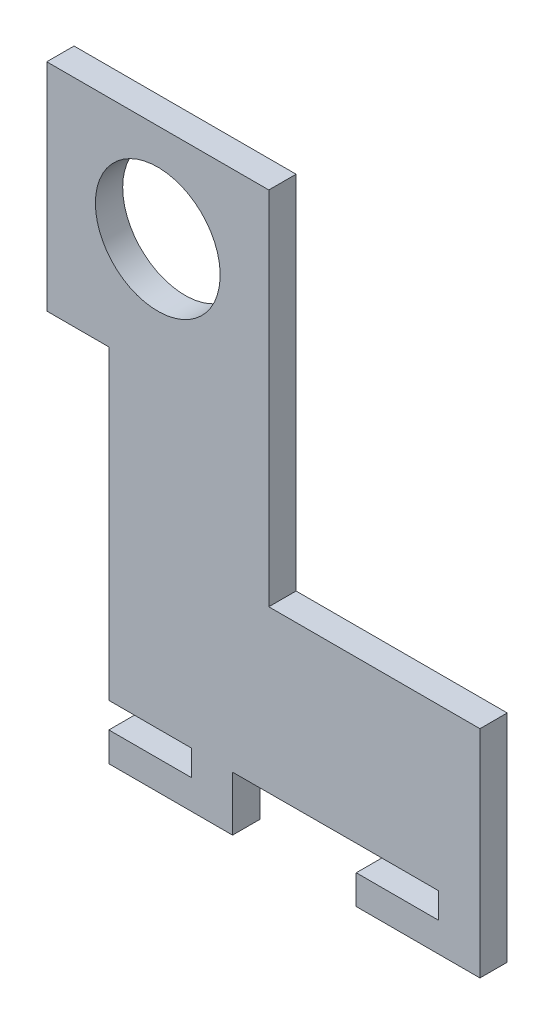
SolidWorks part; units mm, degrees
ref_plane "Front Plane" through (0, 0, 0) normal (0, 0, 1) x (1, 0, 0)
ref_plane "Top Plane" through (0, 0, 0) normal (0, 1, 0) x (1, 0, 0)
ref_plane "Right Plane" through (0, 0, 0) normal (1, 0, 0) x (0, 0, -1)
sketch "Sketch1" plane through (0, 0, 0) normal (0, 0, 1) x (1, 0, 0)
  line L1 (0, 0) -> (76.2, 0)
  line L2 (0, 0) -> (0, 96.6555)
  line L3 (0, 96.6555) -> (76.2, 96.6555)
  line L4 (76.2, 0) -> (76.2, 96.6555)
  line L5 (0, 0) -> (76.2, 96.6555) construction
  line L6 (0, 96.6555) -> (76.2, 0) construction
  point P4 (38.1, 48.3277)
  dimension "D1" = 96.6555
extrude "Boss-Extrude1" add sketch "Sketch1" along normal blind 4.8
sketch "Sketch2" plane through (0, 0, 0) normal (0, 0, -1) x (-1, 0, 0)
  circle A1 centre (-19.5293, 79.4008) radius 10.9746
  dimension "D1" = 21.9492
extrude "Cut-Extrude1" cut sketch "Sketch2" against normal through all
sketch "Sketch3" plane through (0, 0, 0) normal (0, -1, 0) x (1, 0, 0)
  line L1 (0, 0) -> (76.2, 0)
  line L2 (0, 0) -> (0, 4.8)
  line L3 (0, 4.8) -> (76.2, 4.8)
  line L4 (76.2, 0) -> (76.2, 4.8)
  line L5 (0, 0) -> (76.2, 4.8) construction
  line L6 (0, 4.8) -> (76.2, 0) construction
  point P4 (38.1, 2.4)
extrude "Boss-Extrude2" add sketch "Sketch3" along normal blind 4.826
sketch "Sketch5" plane through (0, 0, 0) normal (0, 0, -1) x (-1, 0, 0)
  line L1 (-76.2, 96.6555) -> (-39.0586, 96.6555)
  line L2 (-76.2, 96.6555) -> (-76.2, 33.1555)
  line L3 (-76.2, 33.1555) -> (-39.0586, 33.1555)
  line L4 (-39.0586, 96.6555) -> (-39.0586, 33.1555)
  line L5 (-76.2, 96.6555) -> (-39.0586, 33.1555) construction
  line L6 (-76.2, 33.1555) -> (-39.0586, 96.6555) construction
  point P4 (-57.6293, 64.9055)
  dimension "D1" = 37.1414
  dimension "D2" = 63.5
extrude "Cut-Extrude3" cut sketch "Sketch5" against normal through all
sketch "Sketch6" plane through (0, 0, 0) normal (0, 0, -1) x (-1, 0, 0)
  line L1 (0, -4.826) -> (-10.922, -4.826)
  line L2 (0, -4.826) -> (0, 58.674)
  line L3 (0, 58.674) -> (-10.922, 58.674)
  line L4 (-10.922, -4.826) -> (-10.922, 58.674)
  line L5 (0, -4.826) -> (-10.922, 58.674) construction
  line L6 (0, 58.674) -> (-10.922, -4.826) construction
  point P4 (-5.461, 26.924)
  dimension "D1" = 63.5
  dimension "D2" = 10.922
extrude "Cut-Extrude4" cut sketch "Sketch6" against normal blind 4.826
sketch "Sketch7" plane through (0, 0, 0) normal (0, 0, -1) x (-1, 0, 0)
  line L0 (-10.922, -4.826) -> (-76.2, -4.826) construction
  line L1 (-54.4407, -4.826) -> (-32.6813, -4.826)
  line L2 (-54.4407, -4.826) -> (-54.4407, 4.826)
  line L3 (-54.4407, 4.826) -> (-32.6813, 4.774)
  line L4 (-32.6813, -4.826) -> (-32.6813, 4.774)
  line L5 (-54.4407, -4.826) -> (-32.6813, 4.774) construction
  line L6 (-54.4407, 4.826) -> (-32.6813, -4.826) construction
  line L7 (-76.2, -4.826) -> (-54.4407, -4.826) construction
  line L8 (-10.922, -4.826) -> (-32.6813, -4.826) construction
  line L14 (-10.922, 58.674) -> (-10.922, -4.826) construction
  line L15 (-10.922, 4.826) -> (-25.4242, 4.826)
  line L21 (-10.922, 4.826) -> (-10.922, 0.326)
  line L22 (-10.922, 0.326) -> (-25.4242, 0.326)
  line L23 (-25.4242, 4.826) -> (-25.4242, 0.326)
  line L24 (-10.922, 4.826) -> (-25.4242, 0.326) construction
  line L25 (-10.922, 0.326) -> (-25.4242, 4.826) construction
  line L27 (-54.4407, 4.826) -> (-68.9429, 4.826)
  line L28 (-54.4407, 4.826) -> (-54.4407, 0.326)
  line L29 (-54.4407, 0.326) -> (-68.9429, 0.326)
  line L30 (-68.9429, 4.826) -> (-68.9429, 0.326)
  line L31 (-54.4407, 4.826) -> (-68.9429, 0.326) construction
  line L32 (-54.4407, 0.326) -> (-68.9429, 4.826) construction
  line L38 (-76.2, -4.826) -> (-76.2, 33.1555) construction
  point P4 (-43.5316, -0.013)
  point P15 (-18.1731, 2.576)
  point P21 (-61.6918, 2.576)
  line M13 (-10.922, -4.826) -> (-10.922, 58.674)
  line M20 (-76.2, -4.826) -> (-10.922, -4.826)
  dimension "D1" = 9.6
  dimension "D2" = 4.5
  dimension "D3" = 4.5
  dimension "D4" = 7.2571
  dimension "D5" = 7.2571
extrude "Cut-Extrude6" cut sketch "Sketch7" against normal through all contours L27 L30 L29 L2 | L4 L3 L2 M20 | L15 L23 L22 M13 region at (43.5708, -0.013, 0) region at (18.1731, 2.576, 0) region at (61.6918, 2.576, 0)
equation "\"MDF\"= 4.8mm"
equation "\"Foamcore\"= 4.6mm"
equation "\"PCB\" = 1.6mm"
equation "\"GMaterial\"= \"MDF\""
equation "\"BaseWidth\" = 10in"
equation "\"SkidLength\" = 1in"
equation "\"SkidClearance\" = 0.4in"
equation "\"MotorMountLength\" = 2in"
equation "\"MotorMountWidth\" = \"GMaterial\""
equation "\"MotorMountHeight\" = 2.25in"
equation "\"UnoStackWidth\" = 77.4mm"
equation "\"UnoStackLength\" = 79.8mm"
equation "\"UnoStackHeight\" = 34.2mm"
equation "\"TallHexRiserHeight\" = 22.2mm"
equation "\"PingPongBallSize\" = 40mm"
equation "\"BarrelLength\" = 9in"
equation "\"BarrelSize\" = \"PingPongBallSize\""
equation "\"PlatformLength\" = 4in"
equation "\"PlatformWidth\" = 6in"
equation "\"WheelDiameter\"=2.99213"
equation "\"ServoMountLength\"= 1.53774"
equation "\"ServoGearHeight\" = 0.95330261in"
equation "\"PlatformMountHeight\" = 3.19"
equation "\"PivotHoleRadius\"= 0.616358"
equation "\"D1@Sketch1\"=\"MDF\"+\"PivotHoleRadius\"+3"
equation "\"ServoMountReductionBackHeight\"=2.25"
equation "\"ServoMountHeight\"=2.49223"
equation "\"TensionOffSet\"= .3mm"
equation "\"MotorMountWedge\"=0.333333"
equation "\"LaserCutterOffset\"= .3mm"
equation "\"BumperWidth\"=11"
equation "\"PitcherWheelCompression\" = 2.5mm"
equation "\"PitchingWheelWidth\" = 26.2mm"
equation "\"PitchingWheelDiameter\" = 65.5mm"
equation "\"PitchingWheelMountOffset\" = 8.4mm"
equation "\"PitchingWheelInnerDiameter\" = 45.5mm"
equation "\"PitchingWheelBoltShoulder\" = 4.5mm"
equation "\"BrassCouplingLength\" = 18mm"
equation "\"PitchingMotorHeight\" = 57.0mm"
equation "\"PitchingMotorShaftTopHeight\" = \"PitchingMotorHeight\" - 44.1mm"
equation "\"PitchingMotorBodyHeight\" = 38mm"
equation "\"PitchingMotorTopShoulderHeight\" = 40.6mm - \"PitchingMotorBodyHeight\" "
equation "\"PitchingMotorBottomShoulderHeight\" = 40.2mm - \"PitchingMotorBodyHeight\""
equation "\"PitchingMotorBottomShaftHeight\" = \"PitchingMotorHeight\" - \"PitchingMotorShaftTopHeight\" - \"PitchingMotorTopShoulderHeight\" - \"PitchingMotorBodyHeight\" - \"PitchingMotorBottomShoulderHeight\""
equation "\"PitchingMotorShaftDiameter\" = 2.2mm"
equation "\"PitchingMotorBodyDiameter\" = 27.4mm"
equation "\"PitchingMotorTopShoulderDiameter\" = 9.8mm"
equation "\"PitchingMotorBottomShoulderDiameter\" = 9.8mm"
equation "\"BrassCouplingHexSize\" = 12mm"
equation "\"BrassCouplingBoreSize\" = 3.17mm"
equation "\"PitchingMotorMountingHoleDistance\" = 16mm"
equation "\"Acrylic\" = 4.4mm"
equation "\"PitchingMotorDistance\" = \"PitchingWheelDiameter\" + \"PingPongBallSize\" - \"PitcherWheelCompression\"*2"
equation "\"PitchingMotorPlatformOffset\"=1"
equation "\"ServoPlatformOffset\"=1.64173"
equation "\"BallBearingDiameter\" = 22mm"
equation "\"BallBearingWidth\" = 9mm"
equation "\"BallBearingHexShoulder\" = 9mm - 5.9mm"
equation "\"BallBearingHexSize\" = .36in"
equation "\"WheelWidth\"= 26mm"
equation "\"PlatformMountBackReductionHeight\"= 2.5in"
equation "\"PlatformMountBackReductionWidth\"= 3/7in"
equation "\"PlatformMountFrontReductionWidth\" =  1.46226in"
equation "\"PlatformMountFrontReductionHeight\" = 2.5in"
equation "\"D1@Sketch5\"=\"PlatformMountFrontReductionWidth\""
equation "\"D2@Sketch5\"=\"PlatformMountFrontReductionHeight\""
equation "\"D1@Sketch7\"=\"GMaterial\"*2"
equation "\"PlatformBottomWidthThird\" =  0.857143in"
equation "\"D2@Sketch7\"=\"GMaterial\"-\"LaserCutterOffset\""
equation "\"D3@Sketch7\"=\"GMaterial\"-\"LaserCutterOffset\""
equation "\"D4@Sketch7\"=\"PlatformBottomWidthThird\"/3"
equation "\"D5@Sketch7\"=\"PlatformBottomWidthThird\"/3"
equation "\"PlatformMountFootLength\"=0.857143"
equation "\"D1@Sketch2\"=\"BallBearingDiameter\"-0.002"
